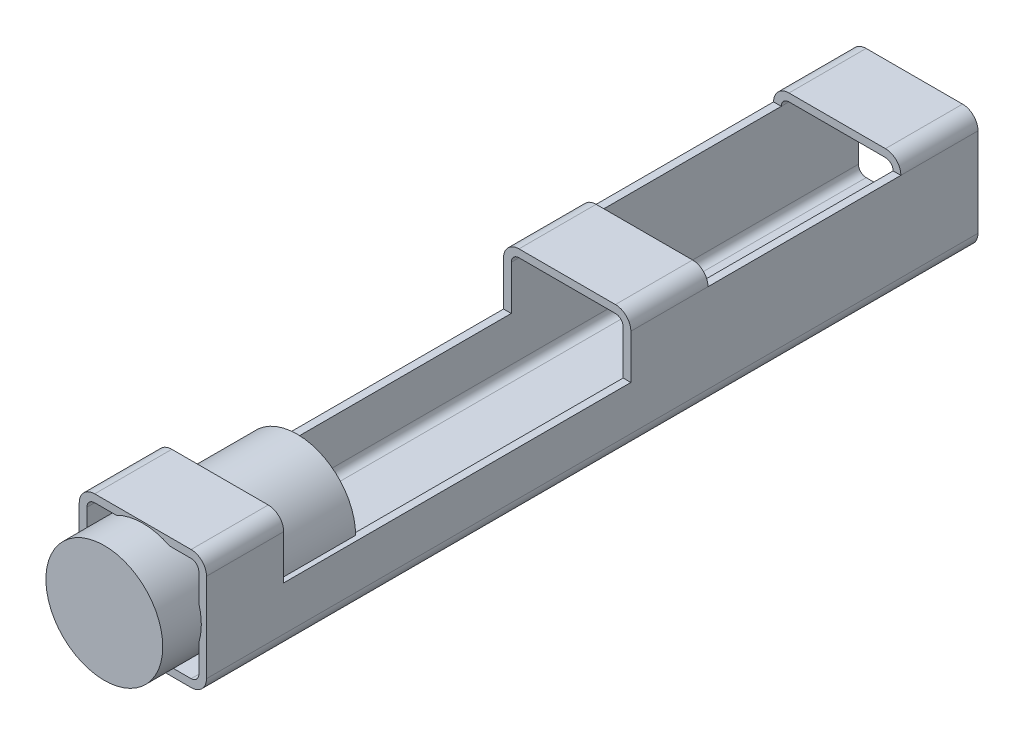
SolidWorks part; units mm, degrees
ref_plane "Front Plane" through (0, 0, 0) normal (0, 0, 1) x (1, 0, 0)
ref_plane "Top Plane" through (0, 0, 0) normal (0, 1, 0) x (1, 0, 0)
ref_plane "Right Plane" through (0, 0, 0) normal (1, 0, 0) x (0, 0, -1)
sketch "Sketch1" plane through (0, 0, 0) normal (0, 0, 1) x (1, 0, 0)
  line L0 (-0.725, -0.575) -> (-0.725, 0.575)
  line L1 (0.625, -0.775) -> (-0.625, -0.775)
  line L2 (0.825, -0.575) -> (0.825, 0.575)
  line L3 (0.625, 0.775) -> (-0.625, 0.775)
  line L4 (-0.825, -0.575) -> (-0.825, 0.575)
  line L5 (0.825, -0.775) -> (-0.825, 0.775) construction
  line L6 (0.825, 0.775) -> (-0.825, -0.775) construction
  line L7 (0.625, 0.675) -> (-0.625, 0.675)
  line L8 (0.725, -0.575) -> (0.725, 0.575)
  line L9 (0.625, -0.675) -> (-0.625, -0.675)
  arc A0 (0.625, -0.775) -> (0.825, -0.575) centre (0.625, -0.575) ccw
  arc A1 (-0.625, -0.775) -> (-0.825, -0.575) centre (-0.625, -0.575) cw
  arc A2 (0.825, 0.575) -> (0.625, 0.775) centre (0.625, 0.575) ccw
  arc A3 (-0.625, 0.775) -> (-0.825, 0.575) centre (-0.625, 0.575) ccw
  arc A4 (-0.625, 0.675) -> (-0.725, 0.575) centre (-0.625, 0.575) ccw
  arc A5 (0.725, 0.575) -> (0.625, 0.675) centre (0.625, 0.575) ccw
  arc A6 (0.625, -0.675) -> (0.725, -0.575) centre (0.625, -0.575) ccw
  arc A7 (-0.625, -0.675) -> (-0.725, -0.575) centre (-0.625, -0.575) cw
  point P0 (0, 0)
  dimension "D3" = 0.2
  dimension "D1" = 1.65
  dimension "D2" = 1.55
  dimension "D4" = 0.1
extrude "Body" add sketch "Sketch1" along normal blind 10
sketch "Sketch2" plane through (-0.825, 0, 0) normal (-1, 0, 0) x (0, 0, 1)
  line L0 (10, 0.775) -> (0, 0.775) construction
  line L1 (1, 0.775) -> (3.5, 0.775)
  line L2 (1, 0.775) -> (1, 0.575)
  line L3 (1, 0.575) -> (3.5, 0.575)
  line L4 (3.5, 0.775) -> (3.5, 0.575)
  line L5 (4.5, 0.775) -> (9, 0.775)
  line L6 (4.5, 0.775) -> (4.5, 0)
  line L7 (4.5, 0) -> (9, 0)
  line L8 (9, 0.775) -> (9, 0)
  line L13 (10, 0.575) -> (0, 0.575) construction
  dimension "D1" = 2.5
  dimension "D2" = 1
  dimension "D3" = 1
  dimension "D4" = 1
extrude "Cut-Extrude1" cut sketch "Sketch2" against normal up to surface (1.65 mm away) up to face at (0.825, 0, 5)
sketch "Sketch3" plane through (0, 0, 10) normal (0, 0, 1) x (1, 0, 0)
  circle A4 centre (0, 0) radius 0.7573
extrude "Wire" add sketch "Sketch3" against normal blind 2 and the other way blind 0.5
other "ConnectionPoint" parameters "Diameter"=1.3, "Stub Length"=1
ref_axis "Axis1" through (0, 0, 20.5) along (0, 0, -1)
